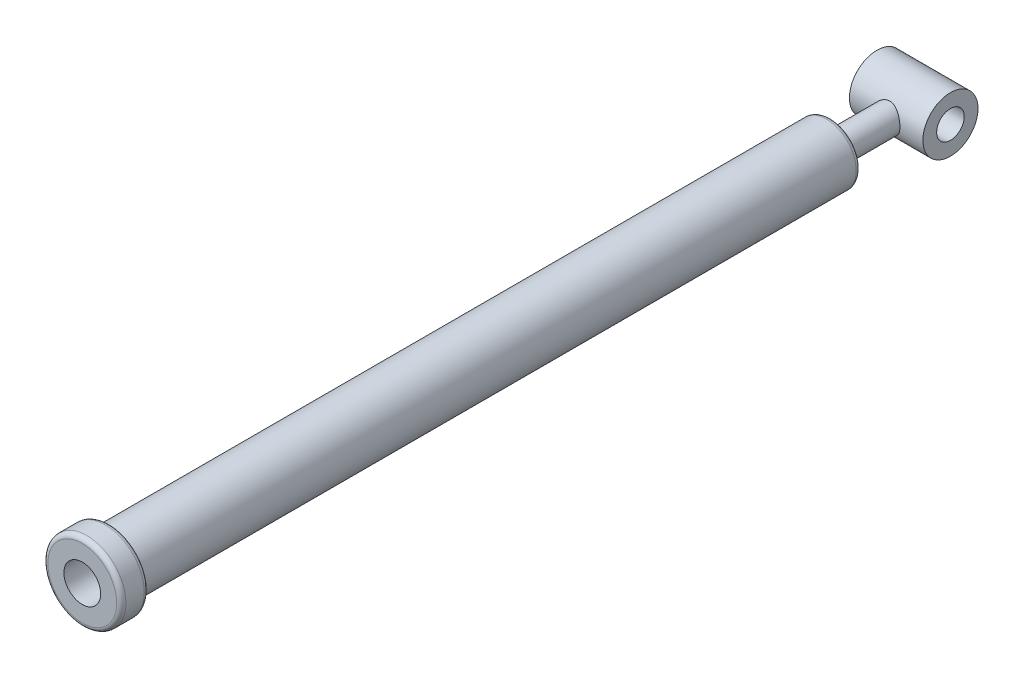
SolidWorks part; units mm, degrees
ref_plane "Front Plane" through (0, 0, 0) normal (0, 0, 1) x (1, 0, 0)
ref_plane "Top Plane" through (0, 0, 0) normal (0, 1, 0) x (1, 0, 0)
ref_plane "Right Plane" through (0, 0, 0) normal (1, 0, 0) x (0, 0, -1)
sketch "Sketch1" plane through (0, 0, 0) normal (0, 0, 1) x (1, 0, 0)
  circle A0 centre (0, 0) radius 42.5
  circle A1 centre (0, 0) radius 20
  dimension "D1" = 85
  dimension "D2" = 40
extrude "Boss-Extrude1" add sketch "Sketch1" against normal blind 30
sketch "Sketch2" plane through (0, 0, -30) normal (0, 0, -1) x (-1, 0, 0)
  circle A0 centre (0, 0) radius 32.5
  circle A1 centre (0, 0) radius 20 construction
  circle A2 centre (0, 0) radius 20
  dimension "D1" = 65
extrude "Boss-Extrude2" add sketch "Sketch2" along normal blind 780
sketch "Sketch6" plane through (0, 0, -810) normal (0, 0, -1) x (-1, 0, 0)
  circle A1 centre (0, 0) radius 32.5
  circle A2 centre (0, 0) radius 32.5
  dimension "D1" = 0
extrude "Boss-Extrude3" add sketch "Sketch6" along normal blind 5
sketch "Sketch7" plane through (0, 0, -815) normal (0, 0, -1) x (-1, 0, 0)
  circle A0 centre (0, 0) radius 15
  dimension "D1" = 30
extrude "Boss-Extrude4" add sketch "Sketch7" along normal blind 65
sketch "Sketch8" plane through (0, 0, 0) normal (1, 0, 0) x (0, 0, -1)
  line L0 (815, -32.5) -> (815, 32.5) construction
  line L1 (880, 0) -> (905, 0) construction
  line L2 (880, -15) -> (880, 15) construction
  circle A0 centre (905, 0) radius 30
  circle A1 centre (905, 0) radius 15
  dimension "D2" = 60
  dimension "D3" = 30
  dimension "D1" = 90
extrude "Boss-Extrude5" add sketch "Sketch8" along normal mid plane 80
fillet "Fillet2" radius 5 3 edges at (42.5, 0, 0) (42.5, 0, -30) (-32.5, 0, -815)
